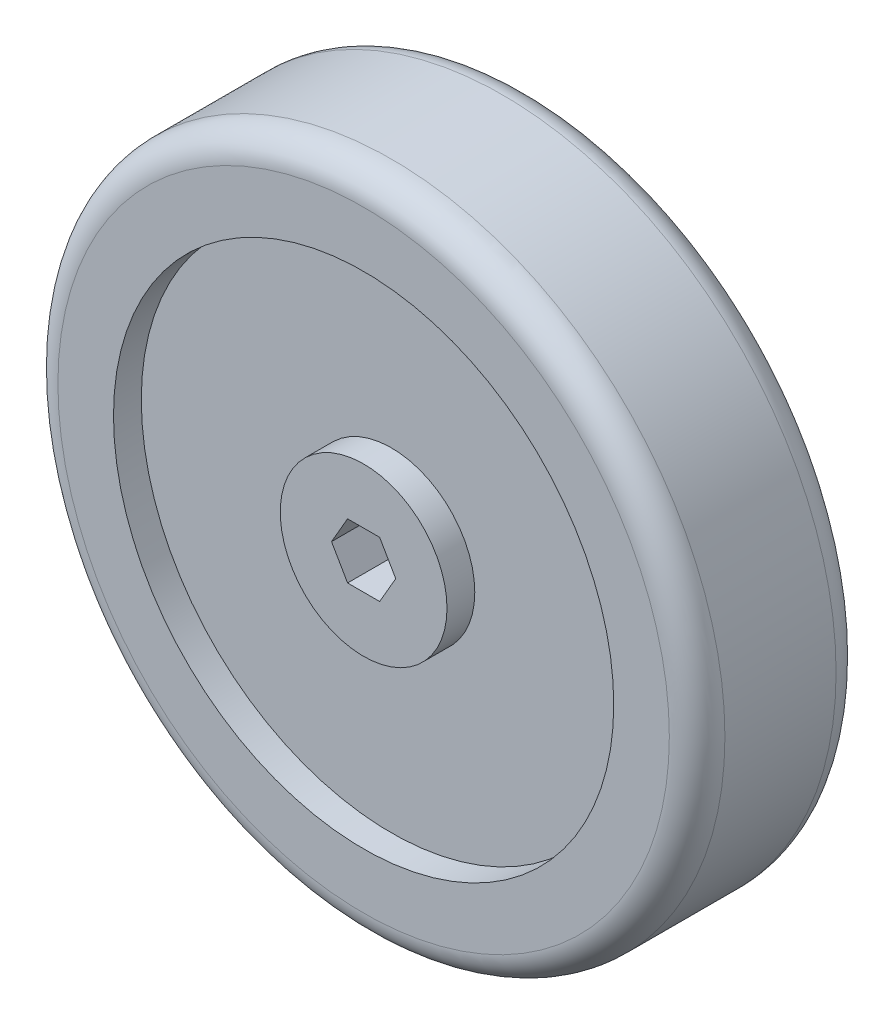
SolidWorks part; units mm, degrees
ref_plane "Front Plane" through (0, 0, 0) normal (0, 0, 1) x (1, 0, 0)
ref_plane "Top Plane" through (0, 0, 0) normal (0, 1, 0) x (1, 0, 0)
ref_plane "Right Plane" through (0, 0, 0) normal (1, 0, 0) x (0, 0, -1)
sketch "Sketch1" plane through (0, 0, 0) normal (0, 0, 1) x (1, 0, 0)
  circle A0 centre (0, 0) radius 76.2
extrude "Boss-Extrude1" add sketch "Sketch1" along normal blind 38.1
fillet "Fillet1" radius 6.35 2 edges at (76.2, 0, 0) (76.2, 0, 38.1)
sketch "Sketch2" plane through (0, 0, 38.1) normal (0, 0, 1) x (1, 0, 0)
  line L1 (7.3323, 0) -> (3.6662, 6.35)
  line L2 (3.6662, 6.35) -> (-3.6662, 6.35)
  line L3 (-3.6662, 6.35) -> (-7.3323, 0)
  line L4 (-7.3323, 0) -> (-3.6662, -6.35)
  line L5 (-3.6662, -6.35) -> (3.6662, -6.35)
  line L6 (3.6662, -6.35) -> (7.3323, 0)
  circle A0 centre (0, 0) radius 6.35 construction
extrude "Cut-Extrude2" cut sketch "Sketch2" against normal through all
sketch "Sketch3" plane through (0, 0, 38.1) normal (0, 0, 1) x (1, 0, 0)
  circle A0 centre (0, 0) radius 19.05
  circle A1 centre (0, 0) radius 57.15
extrude "Cut-Extrude3" cut sketch "Sketch3" against normal blind 6.35
ref_plane "Hor_Plane" through (0, 0, 19.05) normal (0, 0, 1) x (1, 0, 0)
mirror "Mirror1" about plane through (0, 0, 19.05) normal (0, 0, 1) of "Cut-Extrude3"
sketch "Sketch5" plane through (0, 0, 19.05) normal (0, 0, 1) x (1, 0, 0)
  line L1 (-76.2, 76.2) -> (76.2, 76.2)
  line L2 (-76.2, 76.2) -> (-76.2, -76.2)
  line L3 (-76.2, -76.2) -> (76.2, -76.2)
  line L4 (76.2, 76.2) -> (76.2, -76.2)
ref_plane "Plane1" through (0, 2.54, 0) normal (0, 1, 0) x (1, 0, 0)
